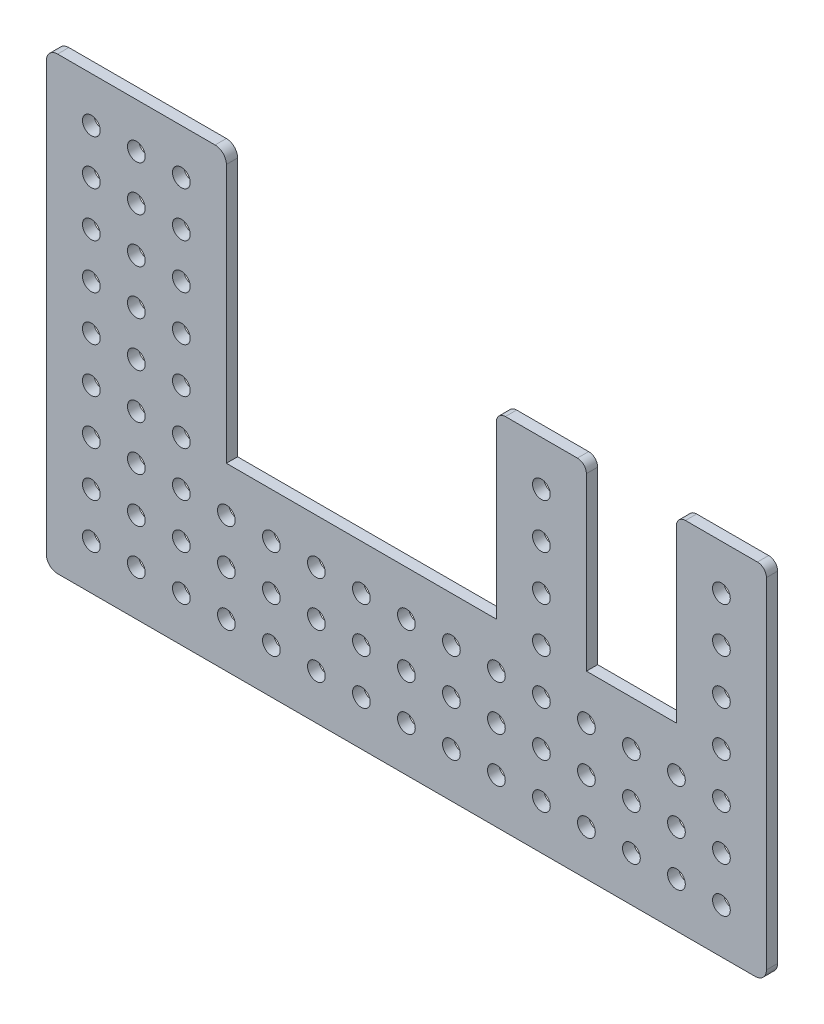
SolidWorks part; units mm, degrees
ref_plane "Front Plane" through (0, 0, 0) normal (0, 0, 1) x (1, 0, 0)
ref_plane "Top Plane" through (0, 0, 0) normal (0, 1, 0) x (1, 0, 0)
ref_plane "Right Plane" through (0, 0, 0) normal (1, 0, 0) x (0, 0, -1)
sketch "Sketch1" plane through (0, 0, 0) normal (0, 0, 1) x (1, 0, 0)
  line L0 (99.0226, 5.3233) -> (102.1976, 5.3233)
  line L1 (-101.0024, 5.3233) -> (99.0226, 5.3233)
  line L2 (-101.0024, 5.3233) -> (-101.0024, -42.3017)
  line L3 (-97.8274, -45.4767) -> (99.0226, -45.4767)
  line L4 (102.1976, 2.1483) -> (102.1976, -42.3017)
  line L6 (-101.0024, 5.3233) -> (-101.0024, 78.3483)
  line L7 (-97.8274, 81.5233) -> (-53.3774, 81.5233)
  line L8 (-50.2024, 5.3233) -> (-50.2024, 78.3483)
  line L9 (102.1976, 5.3233) -> (102.1976, 2.1483)
  arc A0 (-101.0024, -42.3017) -> (-97.8274, -45.4767) centre (-97.8274, -42.3017) ccw
  arc A1 (99.0226, -45.4767) -> (102.1976, -42.3017) centre (99.0226, -42.3017) ccw
  arc A3 (-53.3774, 81.5233) -> (-50.2024, 78.3483) centre (-53.3774, 78.3483) cw
  arc A4 (-101.0024, 78.3483) -> (-97.8274, 81.5233) centre (-97.8274, 78.3483) cw
  point P11 (-101.0024, -45.4767)
  point P14 (102.1976, -45.4767)
  point P17 (102.1976, 5.3233)
  point P20 (-50.2024, 81.5233)
  point P23 (-101.0024, 81.5233)
  dimension "D5" = 3.175
  dimension "D1" = 50.8
  dimension "D2" = 203.2
  dimension "D3" = 50.8
  dimension "D4" = 76.2
extrude "Boss-Extrude1" add sketch "Sketch1" along normal blind 3.175 contours L1 L8 L7 L6 | L4 L1 L2 L3 region at (0.5976, -20.0664, 0) region at (-75.6024, 43.3814, 0)
sketch "Sketch2" plane through (0, 0, 3.175) normal (0, 0, 1) x (1, 0, 0)
  line L0 (-97.8274, 81.5233) -> (-53.3774, 81.5233) construction
  line L1 (-101.0024, -42.3017) -> (-101.0024, 78.3483) construction
  line L2 (102.1976, 5.3233) -> (102.1976, -42.3017) construction
  line L4 (-50.2024, 5.3233) -> (102.1976, 5.3233) construction
  circle A0 centre (-88.3024, 68.8233) radius 2.505
  circle A1 centre (89.4976, -7.3767) radius 2.505
  circle A2 centre (-75.6024, 68.8233) radius 2.505
  circle A3 centre (-62.9024, 68.8233) radius 2.505
  circle A4 centre (-75.6024, 56.1233) radius 2.505
  circle A5 centre (-62.9024, 56.1233) radius 2.505
  circle A6 centre (-75.6024, 43.4233) radius 2.505
  circle A7 centre (-62.9024, 43.4233) radius 2.505
  circle A8 centre (-75.6024, 30.7233) radius 2.505
  circle A9 centre (-62.9024, 30.7233) radius 2.505
  circle A10 centre (-75.6024, 18.0233) radius 2.505
  circle A11 centre (-62.9024, 18.0233) radius 2.505
  circle A12 centre (-75.6024, 5.3233) radius 2.505
  circle A13 centre (-62.9024, 5.3233) radius 2.505
  circle A24 centre (-88.3024, 56.1233) radius 2.505
  circle A25 centre (-88.3024, 43.4233) radius 2.505
  circle A26 centre (-88.3024, 30.7233) radius 2.505
  circle A27 centre (-88.3024, 18.0233) radius 2.505
  circle A28 centre (-88.3024, 5.3233) radius 2.505
  circle A29 centre (-88.3024, -7.3767) radius 2.505
  circle A30 centre (-88.3024, -20.0767) radius 2.505
  circle A31 centre (-88.3024, -32.7767) radius 2.505
  circle A34 centre (76.7976, -7.3767) radius 2.505
  circle A35 centre (64.0976, -7.3767) radius 2.505
  circle A36 centre (51.3976, -7.3767) radius 2.505
  circle A37 centre (38.6976, -7.3767) radius 2.505
  circle A38 centre (25.9976, -7.3767) radius 2.505
  circle A39 centre (13.2976, -7.3767) radius 2.505
  circle A40 centre (0.5976, -7.3767) radius 2.505
  circle A41 centre (76.7976, -20.0767) radius 2.505
  circle A42 centre (64.0976, -20.0767) radius 2.505
  circle A43 centre (51.3976, -20.0767) radius 2.505
  circle A44 centre (38.6976, -20.0767) radius 2.505
  circle A45 centre (25.9976, -20.0767) radius 2.505
  circle A46 centre (13.2976, -20.0767) radius 2.505
  circle A47 centre (0.5976, -20.0767) radius 2.505
  circle A48 centre (76.7976, -32.7767) radius 2.505
  circle A49 centre (64.0976, -32.7767) radius 2.505
  circle A50 centre (51.3976, -32.7767) radius 2.505
  circle A51 centre (38.6976, -32.7767) radius 2.505
  circle A52 centre (25.9976, -32.7767) radius 2.505
  circle A53 centre (13.2976, -32.7767) radius 2.505
  circle A54 centre (0.5976, -32.7767) radius 2.505
  circle A55 centre (89.4976, -20.0767) radius 2.505
  circle A56 centre (89.4976, -32.7767) radius 2.505
  circle A57 centre (-12.1024, -7.3767) radius 2.505
  circle A58 centre (-24.8024, -7.3767) radius 2.505
  circle A59 centre (-37.5024, -7.3767) radius 2.505
  circle A60 centre (-50.2024, -7.3767) radius 2.505
  circle A61 centre (-62.9024, -7.3767) radius 2.505
  circle A62 centre (-75.6024, -7.3767) radius 2.505
  circle A63 centre (-12.1024, -20.0767) radius 2.505
  circle A64 centre (-24.8024, -20.0767) radius 2.505
  circle A65 centre (-37.5024, -20.0767) radius 2.505
  circle A66 centre (-50.2024, -20.0767) radius 2.505
  circle A67 centre (-62.9024, -20.0767) radius 2.505
  circle A68 centre (-75.6024, -20.0767) radius 2.505
  circle A69 centre (-12.1024, -32.7767) radius 2.505
  circle A70 centre (-24.8024, -32.7767) radius 2.505
  circle A71 centre (-37.5024, -32.7767) radius 2.505
  circle A72 centre (-50.2024, -32.7767) radius 2.505
  circle A73 centre (-62.9024, -32.7767) radius 2.505
  circle A74 centre (-75.6024, -32.7767) radius 2.505
  dimension "D1" = 5.01
  dimension "D2" = 5.01
  dimension "D3" = 12.7
  dimension "D4" = 12.7
  dimension "D7" = 12.7
  dimension "D8" = 12.7
  dimension "D9" = 14
  dimension "D10" = 3
extrude "Cut-Extrude1" cut sketch "Sketch2" against normal through all
sketch "Sketch3" plane through (0, 0, 3.175) normal (0, 0, 1) x (1, 0, 0)
  line L0 (-50.2024, 5.3233) -> (102.1976, 5.3233) construction
  line L1 (48.8576, 56.1233) -> (28.5376, 56.1233)
  line L2 (51.3976, 53.5833) -> (51.3976, 5.3233)
  line L3 (51.3976, 5.3233) -> (25.9976, 5.3233)
  line L4 (25.9976, 53.5833) -> (25.9976, 5.3233)
  line L6 (79.3376, 56.1233) -> (99.6576, 56.1233)
  line L7 (76.7976, 53.5833) -> (76.7976, 5.3233)
  line L8 (76.7976, 5.3233) -> (102.1976, 5.3233)
  line L9 (102.1976, 53.5833) -> (102.1976, 5.3233)
  line L10 (-50.2024, 5.3233) -> (-50.2024, 78.3483) construction
  arc A0 (99.6576, 56.1233) -> (102.1976, 53.5833) centre (99.6576, 53.5833) cw
  arc A1 (79.3376, 56.1233) -> (76.7976, 53.5833) centre (79.3376, 53.5833) ccw
  arc A2 (28.5376, 56.1233) -> (25.9976, 53.5833) centre (28.5376, 53.5833) ccw
  arc A3 (48.8576, 56.1233) -> (51.3976, 53.5833) centre (48.8576, 53.5833) cw
  point P14 (102.1976, 56.1233)
  point P17 (76.7976, 56.1233)
  point P20 (25.9976, 56.1233)
  point P23 (51.3976, 56.1233)
  dimension "D7" = 2.54
  dimension "D1" = 50.8
  dimension "D2" = 76.2
  dimension "D3" = 25.4
  dimension "D4" = 25.4
  dimension "D5" = 25.4
  dimension "D6" = 50.8
extrude "Boss-Extrude2" add sketch "Sketch3" against normal up to surface (3.175 mm away) up to face at (-85.7974, 43.4233, 0)
sketch "Sketch4" plane through (0, 0, 3.175) normal (0, 0, 1) x (1, 0, 0)
  line L2 (51.3976, 5.3233) -> (51.3976, 53.5833) construction
  line L3 (48.8576, 56.1233) -> (28.5376, 56.1233) construction
  line L4 (102.1976, 53.5833) -> (102.1976, -42.3017) construction
  line L5 (99.6576, 56.1233) -> (79.3376, 56.1233) construction
  circle A0 centre (38.6976, 43.4233) radius 2.5
  circle A1 centre (89.4976, 43.4233) radius 2.5
  circle A2 centre (38.6976, 30.7233) radius 2.5
  circle A3 centre (38.6976, 18.0233) radius 2.5
  circle A4 centre (38.6976, 5.3233) radius 2.5
  circle A5 centre (89.4976, 30.7233) radius 2.5
  circle A6 centre (89.4976, 18.0233) radius 2.5
  circle A7 centre (89.4976, 5.3233) radius 2.5
  dimension "D1" = 5
  dimension "D4" = 5
  dimension "D2" = 12.7
  dimension "D3" = 12.7
  dimension "D5" = 12.7
  dimension "D6" = 12.7
extrude "Cut-Extrude2" cut sketch "Sketch4" against normal through all
